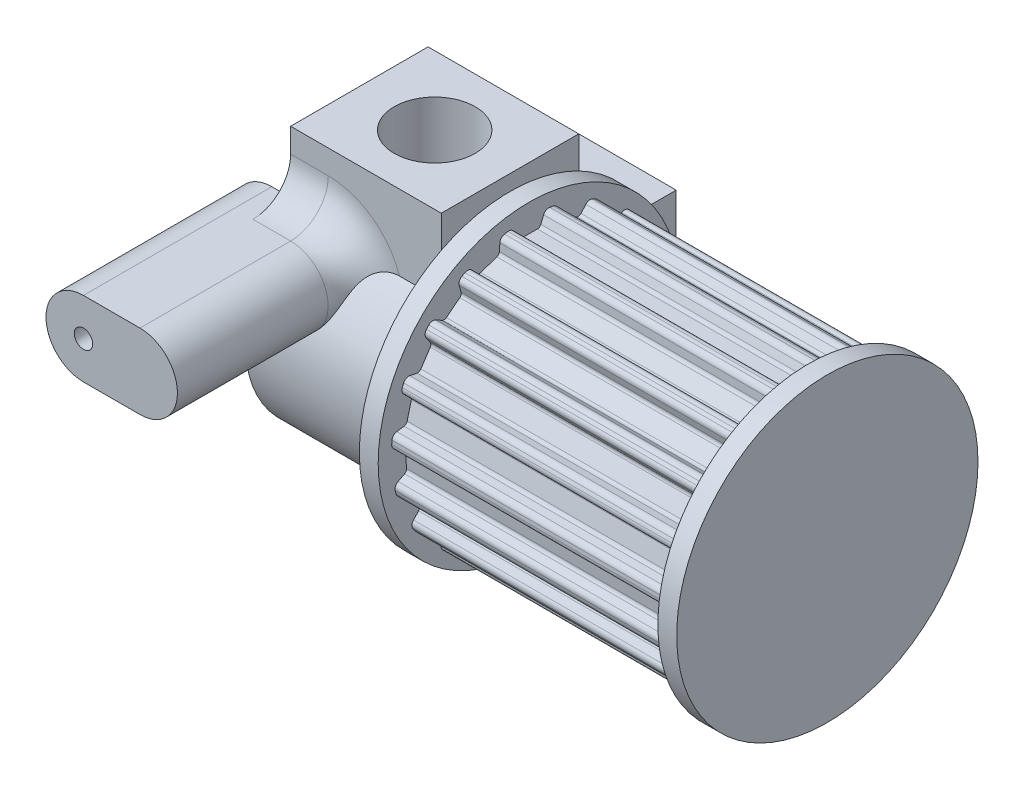
SolidWorks part; units mm, degrees
material "PLA Black"
ref_plane "Front" through (0, 0, 0) normal (0, 0, 1) x (1, 0, 0)
ref_plane "Top" through (0, 0, 0) normal (0, 1, 0) x (1, 0, 0)
ref_plane "Right" through (0, 0, 0) normal (1, 0, 0) x (0, 0, -1)
sketch "Sketch1" plane through (0, 0, 0) normal (1, 0, 0) x (0, 0, -1)
  line L0 (1.118, 1) -> (-1.118, 1) construction
  line L1 (-3.65, 4.8249) -> (3.65, 4.8249)
  line L2 (4.8249, 3.65) -> (4.8249, -3.65)
  line L3 (0, 0) -> (11.6334, 0) construction
  line L4 (0, 0) -> (0, 8.6732) construction
  arc A0 (-1.118, 1) -> (1.118, 1) centre (0, 0) ccw construction
  circle A1 centre (0, 0) radius 1.75
  arc A2 (4.8249, -3.65) -> (-3.65, 4.8249) centre (0, 0) cw
  arc A3 (4.8249, 3.65) -> (3.65, 4.8249) centre (0, 0) ccw
  dimension "D1" = 3
  dimension "D3" = 0.25
  dimension "D5" = 6.05
  dimension "D2" = 1
  dimension "D4" = 7.3
extrude "Boss-Extrude1" add sketch "Sketch1" along normal mid plane 8
sketch "Sketch2" plane through (0, 4.8249, 0) normal (0, 1, 0) x (1, 0, 0)
  circle A0 centre (0, 0) radius 2.15
  dimension "D1" = 4.3
extrude "Cut-Extrude1" cut sketch "Sketch2" against normal blind 5
sketch "Sketch7" plane through (4, 0, 0) normal (1, 0, 0) x (0, 0, -1)
  circle A0 centre (0, 0) radius 1.75 construction
  circle A1 centre (0, 0) radius 7.3
  circle A2 centre (0, 0) radius 1.75
  dimension "D1" = 14.6
extrude "Boss-Extrude5" add sketch "Sketch7" along normal blind 15.85
sketch "Sketch8" plane through (19.85, 0, 0) normal (1, 0, 0) x (0, 0, -1)
  line L0 (-0.4541, 6.5499) -> (0.4528, 6.5499)
  line L1 (0.6374, 6.6734) -> (0.7865, 7.0333)
  line L2 (-0.6389, 6.6734) -> (-0.788, 7.0333)
  line L6 (0, 9.2013) -> (0, 0) construction
  arc A0 (0.4528, 6.5499) -> (0.6374, 6.6734) centre (0.4526, 6.7499) ccw
  arc A1 (-0.4541, 6.5499) -> (-0.6389, 6.6734) centre (-0.4541, 6.7499) cw
  arc A2 (0.7865, 7.0333) -> (1.1093, 7.2152) centre (1.0638, 6.9187) cw
  arc A3 (-0.788, 7.0333) -> (-1.1108, 7.215) centre (-1.0652, 6.9185) ccw
  circle A4 centre (0, 0) radius 7.3 construction
  arc A5 (-1.1108, 7.215) -> (1.1093, 7.2152) centre (0, 0) cw
  point P3 (-0.0007, 6.5499)
  point P15 (0, 9.84)
extrude "Cut-Extrude3" cut sketch "Sketch8" against normal up to surface (15.85 mm away) up to face at (4, 0, -7.3)
pattern_circular "CirPattern1" count 19 over 360 about axis through (19.85, 0, 0) along (-1, 0, 0) of "Cut-Extrude3"
sketch "Sketch9" plane through (19.85, 0, 0) normal (1, 0, 0) x (0, 0, -1)
  circle A0 centre (0, 0) radius 8
  dimension "D1" = 16
extrude "Boss-Extrude6" add sketch "Sketch9" along normal blind 1
sketch "Sketch10" plane through (4, 0, 0) normal (-1, 0, 0) x (0, 0, 1)
  circle A0 centre (0, 0) radius 8
  circle A1 centre (0, 0) radius 8 construction
extrude "Boss-Extrude7" add sketch "Sketch10" against normal blind 1
sketch "Sketch3" plane through (0, 0, -4.8249) normal (0, 0, -1) x (-1, 0, 0)
  circle A0 centre (0, 0) radius 2.15
  dimension "D1" = 4.3
extrude "Cut-Extrude2" cut sketch "Sketch3" against normal blind 5
sketch "Sketch4" plane through (0, 4.8249, 0) normal (0, 1, 0) x (1, 0, 0)
  line L0 (4, 3.65) -> (-4, 3.65) construction
  line L2 (4, -3.65) -> (-4, -3.65) construction
  line L3 (-4, 3.65) -> (-4, -3.65) construction
  line L4 (4, 3.65) -> (-4, 3.65)
  line L5 (4, 3.65) -> (4, -3.65)
  line L6 (4, -3.65) -> (-4, -3.65)
  line L7 (-4, 3.65) -> (-4, -3.65)
  line L8 (4, 7.3) -> (4, -7.3) construction
  circle A0 centre (0, 0) radius 2.15 construction
  circle A1 centre (0, 0) radius 2.15
extrude "Boss-Extrude2" add sketch "Sketch4" along normal blind 4
sketch "Sketch5" plane through (0, 0, -4.8249) normal (0, 0, -1) x (-1, 0, 0)
  line L0 (-4, 3.65) -> (4, 3.65) construction
  line L1 (4, -3.65) -> (4, 3.65) construction
  line L2 (-4, -3.65) -> (4, -3.65) construction
  line L4 (-4, 3.65) -> (4, 3.65)
  line L5 (4, -3.65) -> (4, 3.65)
  line L6 (-4, -3.65) -> (4, -3.65)
  line L7 (-4, -3.65) -> (-4, 3.65)
  line L8 (-4, -7.3) -> (-4, 7.3) construction
  circle A0 centre (0, 0) radius 2.15 construction
  circle A1 centre (0, 0) radius 2.15
extrude "Boss-Extrude3" add sketch "Sketch5" along normal blind 4
ref_axis "Axis1" through (2.15, 0, 0) along (-1, 0, 0)
sketch "Sketch6" plane through (0, 0, 3.65) normal (0, 0, 1) x (1, 0, 0)
  line L0 (-4, 8.8249) -> (-4, 4.8249) construction
  line L2 (-2, 5.5445) -> (-5, 5.5445)
  line L3 (-5, 1.5655) -> (-2, 1.5655)
  line L6 (2.15, 0) -> (-4, 0) construction
  circle A0 centre (-5, 3.555) radius 0.4895
  arc A1 (-5, 5.5445) -> (-5, 1.5655) centre (-5, 3.555) ccw
  arc A2 (-2, 5.5445) -> (-2, 1.5655) centre (-2, 3.555) cw
  dimension "D1" = 0.979
  dimension "D2" = 3.555
  dimension "D3" = 1.5
  dimension "D4" = 1
  dimension "D5" = 3
extrude "Boss-Extrude4" add sketch "Sketch6" along normal blind 10
fillet "Fillet1" radius 2 2 edges at (-1.154, 5.3556, 3.65) (-3, 5.5445, 3.65)
equation "\"knee_angle\"= 70"
equation "\"ankle_angle\" = 80"
equation "\"hip_angle\" = 40"
equation "\"spring_ankle_parallel_arm_diameter\"= 0.89"
equation "\"spring_ankle_parallel_arm_length\"= 13"
equation "\"spring_ankle_parallel_intern_diameter\"= 6.22"
equation "\"spring_ankle_parallel_angle\"= \"ankle_angle\""
equation "\"spring_ankle_parallel_turns\"= 3"
equation "\"spring_ankle_parallel_pitch\"= \"spring_ankle_parallel_arm_diameter\" * 1.01"
equation "\"spring_ankle_parallel_cutting_distance\"= (1-\"spring_ankle_parallel_angle\" / 360) * \"spring_ankle_parallel_pitch\""
equation "\"spring_ankle_serial_arm_diameter\"= 0.89"
equation "\"spring_ankle_serial_arm_length\"= 10"
equation "\"spring_ankle_serial_intern_diameter\"= 6.22"
equation "\"spring_ankle_serial_angle\"= \"90\""
equation "\"spring_ankle_serial_turns\"= 3"
equation "\"spring_ankle_serial_pitch\"= \"spring_ankle_serial_arm_diameter\" * 1.01"
equation "\"spring_ankle_serial_cutting_distance\"= (1-\"spring_ankle_serial_angle\" / 360) * \"spring_ankle_serial_pitch\""
equation "\"spring_knee_parallel_arm_diameter\"= 0.89"
equation "\"spring_knee_parallel_arm_length\"= 15"
equation "\"spring_knee_parallel_intern_diameter\"= 5.46"
equation "\"spring_knee_parallel_angle\"= -\"knee_angle\" + 90"
equation "\"spring_knee_parallel_turns\"= 3"
equation "\"spring_knee_parallel_pitch\"= \"spring_knee_parallel_arm_diameter\" * 1.01"
equation "\"spring_knee_parallel_cutting_distance\"= (1-(\"spring_knee_parallel_angle\") / 360) * \"spring_knee_parallel_pitch\""
equation "\"spring_knee_serial_arm_diameter\"= 0.89"
equation "\"spring_knee_serial_arm_length\"= 10"
equation "\"spring_knee_serial_intern_diameter\"= 5.46"
equation "\"spring_knee_serial_angle\"= \"90\""
equation "\"spring_knee_serial_turns\"= 3"
equation "\"spring_knee_serial_pitch\"= \"spring_knee_serial_arm_diameter\" * 1.01"
equation "\"spring_knee_serial_cutting_distance\"= (1-\"spring_knee_serial_angle\" / 360) * \"spring_knee_serial_pitch\""
equation "\"D2@Sketch6\" = ( \"spring_ankle_serial_intern_diameter\" + \"spring_ankle_serial_arm_diameter\" ) / 2"
equation "\"D1@Sketch6\" = \"spring_ankle_serial_arm_diameter\" * 1.1"
